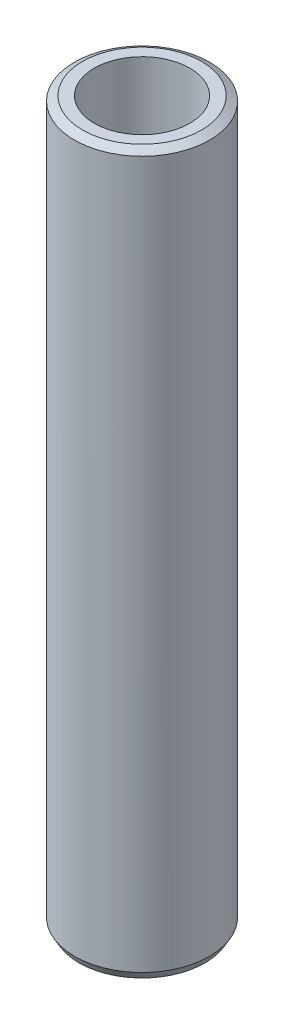
SolidWorks part; units mm, degrees
ref_plane "Front Plane" through (0, 0, 0) normal (0, 0, 1) x (1, 0, 0)
ref_plane "Top Plane" through (0, 0, 0) normal (0, 1, 0) x (1, 0, 0)
ref_plane "Right Plane" through (0, 0, 0) normal (1, 0, 0) x (0, 0, -1)
sketch "Sketch1" plane through (0, 0, 0) normal (0, 1, 0) x (1, 0, 0)
  circle A0 centre (0, 0) radius 40
  dimension "SHAFT_OD" = 80
extrude "Boss-Extrude1" add sketch "Sketch1" along normal blind 425.9903
sketch "Sketch2" plane through (0, 0, 0) normal (0, 1, 0) x (1, 0, 0)
  circle A0 centre (0, 0) radius 28.3068
  dimension "BORE_D" = 56.6137
extrude "Cut-Extrude1" cut sketch "Sketch2" along normal through all
chamfer "Chamfer1" distance 2.7665 angle 60 2 edges at (0, 425.9903, 40) (0, 0, 40) first distance on face at (0, 425.9903, 40) first distance on face at (0, 0, 28.3068)
